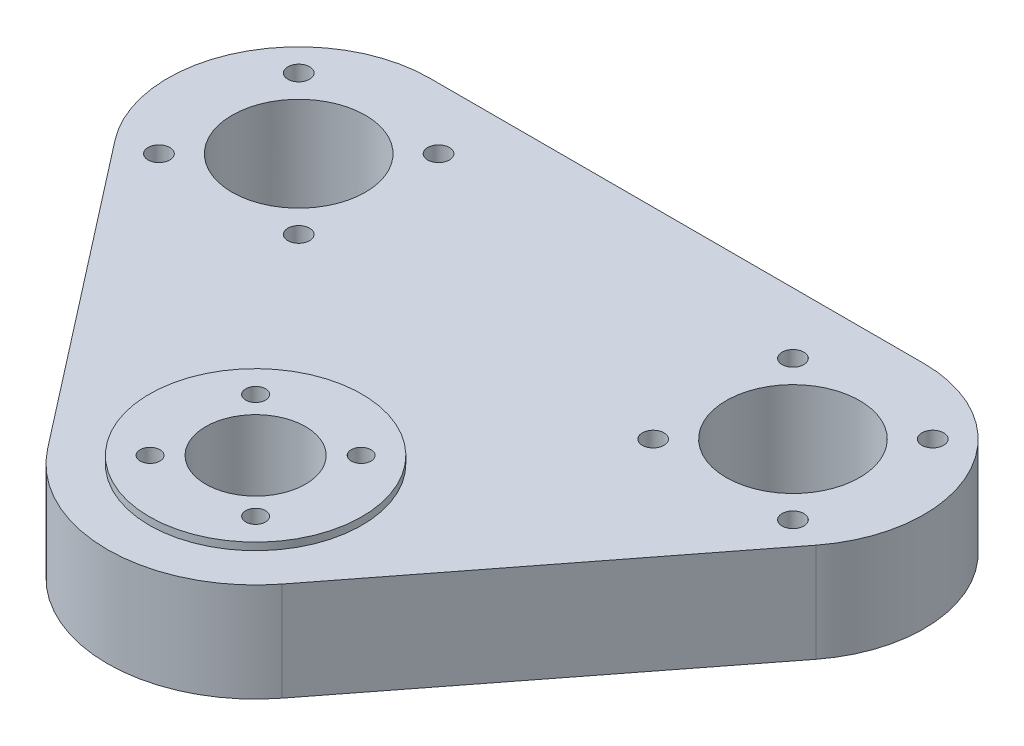
SolidWorks part; units mm, degrees
ref_plane "Front Plane" through (0, 0, 0) normal (0, 0, 1) x (1, 0, 0)
ref_plane "Top Plane" through (0, 0, 0) normal (0, 1, 0) x (1, 0, 0)
ref_plane "Right Plane" through (0, 0, 0) normal (1, 0, 0) x (0, 0, -1)
sketch "Sketch1" plane through (0, 0, 0) normal (0, 1, 0) x (1, 0, 0)
  line L0 (0, 0) -> (50, 58.7219) construction
  line L1 (50, 58.7219) -> (-50, 58.7219) construction
  line L2 (-50, 58.7219) -> (0, 0) construction
  line L3 (-70.9356, 42.4754) -> (-23.7007, -18.3923)
  line L4 (-50, 85.2219) -> (50, 85.2219)
  line L5 (23.7007, -18.3923) -> (70.9356, 42.4754)
  circle A0 centre (-50, 58.7219) radius 26.5 construction
  circle A1 centre (50, 58.7219) radius 26.5 construction
  circle A2 centre (0, 0) radius 30 construction
  arc A3 (-70.9356, 42.4754) -> (-50, 85.2219) centre (-50, 58.7219) cw
  arc A4 (50, 85.2219) -> (70.9356, 42.4754) centre (50, 58.7219) cw
  arc A5 (-23.7007, -18.3923) -> (23.7007, -18.3923) centre (0, 0) ccw
  dimension "D3" = 53
  dimension "D4" = 60
  dimension "D1" = 100
  dimension "D2" = 77.125
extrude "Boss-Extrude1" add sketch "Sketch1" along normal blind 20 contours A5 L5 A4 L4 A3 L3
sketch "Sketch3" plane through (0, 20, 0) normal (0, 1, 0) x (1, 0, 0)
  circle A0 centre (0, 0) radius 30 construction
  circle A1 centre (0, 0) radius 30 construction
  circle A2 centre (0, 0) radius 21.5
  dimension "D1" = 43
extrude "Boss-Extrude2" add sketch "Sketch3" along normal blind 1.5
sketch "Sketch4" plane through (0, 0, 0) normal (0, -1, 0) x (1, 0, 0)
  line L0 (0, -1000) -> (0, 49000) construction
  line L1 (-30, 0) -> (30, 0) construction
  line L2 (-76.5, -58.7219) -> (-23.5, -58.7219) construction
  line L3 (50, -58.7219) -> (-50, -58.7219) construction
  line L4 (-50, -32.2219) -> (-50, -85.2219) construction
  line L5 (-10.6773, 10.6773) -> (0, 0) construction
  line L6 (-10.6773, -10.6773) -> (0, 0) construction
  line L7 (-64.1421, -44.5798) -> (-50, -58.7219) construction
  circle A0 centre (50, -58.7219) radius 26.5 construction
  circle A1 centre (0, 0) radius 30 construction
  circle A2 centre (-50, -58.7219) radius 26.5 construction
  circle A3 centre (50, -58.7219) radius 26.5 construction
  circle A4 centre (0, 0) radius 30 construction
  circle A5 centre (-50, -58.7219) radius 26.5 construction
  circle A6 centre (0, 0) radius 10.1
  circle A7 centre (-50, -58.7219) radius 13.5
  circle A10 centre (-10.6773, 10.6773) radius 2
  arc A12 (-70.9356, -42.4754) -> (-50, -85.2219) centre (-50, -58.7219) ccw construction
  circle A13 centre (-10.6773, -10.6773) radius 2
  circle A14 centre (-64.1421, -44.5798) radius 2.2
  circle A15 centre (-64.1421, -72.8641) radius 2.2
  circle A16 centre (-35.8579, -72.8641) radius 2.2
  circle A17 centre (-35.8579, -44.5798) radius 2.2
  circle A18 centre (50, -58.7219) radius 13.5
  circle A19 centre (64.1421, -72.8641) radius 2.2
  circle A20 centre (35.8579, -72.8641) radius 2.2
  circle A21 centre (35.8579, -44.5798) radius 2.2
  circle A22 centre (64.1421, -44.5798) radius 2.2
  circle A23 centre (10.6773, -10.6773) radius 2
  circle A24 centre (10.6773, 10.6773) radius 2
  dimension "D1" = 20.2
  dimension "D2" = 27
  dimension "D4" = 4
  dimension "D5" = 45
  dimension "D7" = 4.4
  dimension "D3" = 15.1
  dimension "D6" = 20
  dimension "D8" = 45
extrude "Cut-Extrude1" cut sketch "Sketch4" against normal through all
